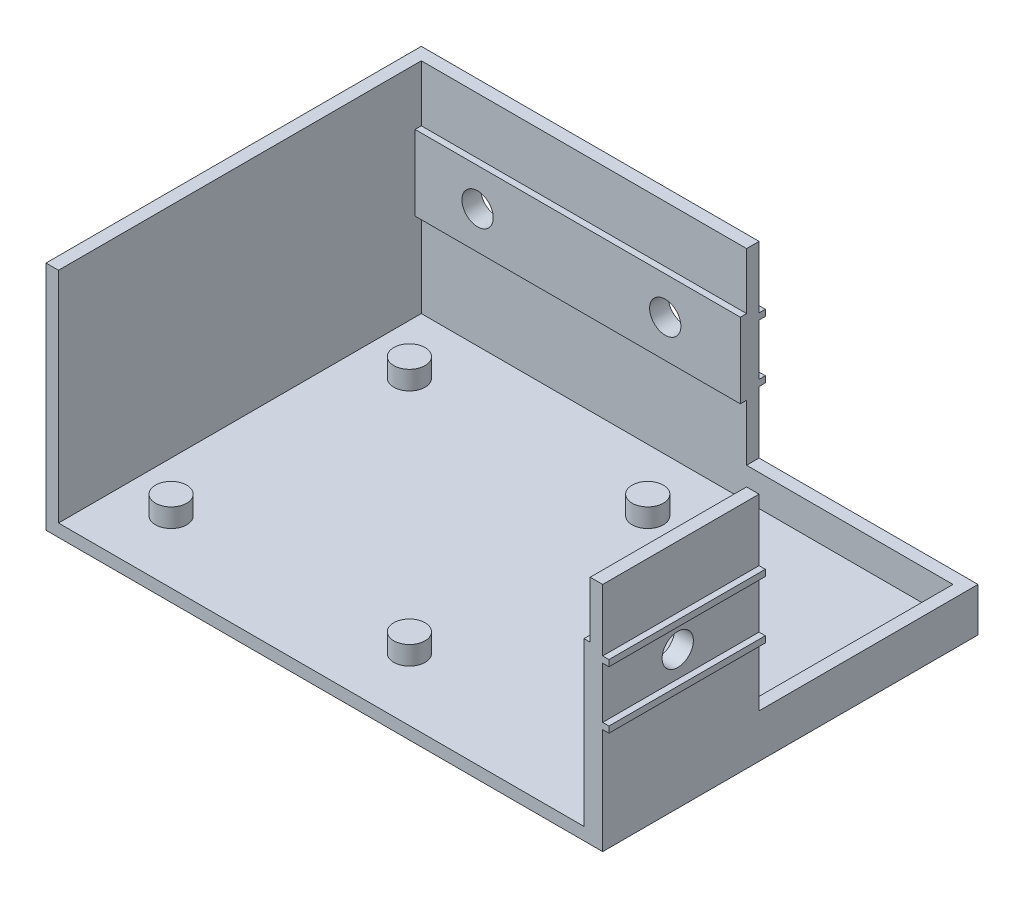
SolidWorks part; units mm, degrees
ref_plane "前视基准面" through (0, 0, 0) normal (0, 0, 1) x (1, 0, 0)
ref_plane "上视基准面" through (0, 0, 0) normal (0, 1, 0) x (1, 0, 0)
ref_plane "右视基准面" through (0, 0, 0) normal (1, 0, 0) x (0, 0, -1)
sketch "底座图" plane through (0, 0, 0) normal (0, 1, 0) x (1, 0, 0)
  line L1 (0, 60) -> (89, 60)
  line L2 (0, 60) -> (0, 0)
  line L3 (0, 0) -> (89, 0)
  line L4 (89, 60) -> (89, 0)
  dimension "D1" = 60
  dimension "D2" = 89
extrude "底座" add sketch "底座图" along normal blind 2
sketch "螺丝柱接口" plane through (0, 2, 0) normal (0, 1, 0) x (1, 0, 0)
  line L1 (0, 0) -> (89, 0) construction
  line L3 (0, 60) -> (0, 0) construction
  circle A0 centre (10, 10) radius 2.5
  circle A1 centre (48.1, 10) radius 2.5
  circle A2 centre (48.1, 48.1) radius 2.5
  circle A3 centre (10, 48.1) radius 2.5
  dimension "D5" = 38.1
  dimension "D7" = 5
  dimension "D1" = 10
  dimension "D2" = 10
  dimension "D4" = 2
  dimension "D6" = 38.1
  dimension "D3" = 2
extrude "螺丝柱" add sketch "螺丝柱接口" along normal blind 3
sketch "侧壁图" plane through (0, 2, 0) normal (0, 1, 0) x (1, 0, 0)
  line L8 (2, 58) -> (2, 2)
  line L9 (2, 2) -> (87, 2)
  line L10 (87, 2) -> (87, 58)
  line L11 (87, 58) -> (2, 58)
  line L12 (2, 58) -> (2, 0)
  line L14 (87, 0) -> (87, 58)
  line L15 (87, 58) -> (2, 58)
  dimension "D1" = 2
extrude "侧壁" add sketch "侧壁图" along normal blind 35 thin thin type one direction wall 2
sketch "草图4" plane through (0, 37, 0) normal (0, 1, 0) x (1, 0, 0)
  line L1 (89, 60) -> (54, 60)
  line L2 (89, 60) -> (89, 25)
  line L3 (89, 25) -> (54, 25)
  line L4 (54, 60) -> (54, 25)
  dimension "D1" = 35
  dimension "D2" = 35
extrude "连接件缺口处" cut sketch "草图4" against normal blind 30
sketch "草图8" plane through (87, 0, 0) normal (-1, 0, 0) x (0, 0, 1)
  line L0 (-25, 7) -> (-25, 37) construction
  line L1 (-25, 28) -> (0, 28)
  line L2 (-25, 28) -> (-25, 2)
  line L3 (-25, 2) -> (0, 2)
  line L4 (0, 28) -> (0, 2)
  line L6 (0, 37) -> (-25, 37) construction
  line L7 (0, 2) -> (-58, 2) construction
  dimension "D1" = 9
  dimension "D2" = 0
extrude "内凸层（侧）" add sketch "草图8" along normal blind 1
sketch "草图10" plane through (86, 0, 0) normal (-1, 0, 0) x (0, 0, 1)
  line L0 (0, 37) -> (-25, 37) construction
  line L4 (0, 2) -> (0, 28) construction
  circle A0 centre (-12, 22) radius 2.5
  dimension "D1" = 5
  dimension "D2" = 15
  dimension "D3" = 12
extrude "安装孔（侧）" cut sketch "草图10" against normal through all
sketch "草图11" plane through (89, 0, 0) normal (1, 0, 0) x (0, 0, -1)
  line L0 (0, 37) -> (0, 0) construction
  line L1 (0, 27.1) -> (25, 27.1)
  line L2 (0, 27.1) -> (0, 26.1)
  line L3 (0, 26.1) -> (25, 26.1)
  line L4 (25, 27.1) -> (25, 26.1)
  line L5 (25, 7) -> (25, 37) construction
  line L7 (25, 16.9) -> (25, 17.9)
  line L8 (0, 17.9) -> (25, 17.9)
  line L9 (0, 16.9) -> (0, 17.9)
  line L10 (0, 16.9) -> (25, 16.9)
  dimension "D3" = 4.1
  dimension "D1" = 1
extrude "安装纹路（侧）" add sketch "草图11" along normal blind 1
sketch "草图7" plane through (0, 0, -58) normal (0, 0, 1) x (1, 0, 0)
  line L0 (54, 37) -> (54, 7) construction
  line L1 (54, 28) -> (2, 28)
  line L2 (54, 28) -> (54, 16)
  line L3 (54, 16) -> (2, 16)
  line L4 (2, 28) -> (2, 16)
  line L5 (2, 37) -> (2, 2) construction
  line L6 (54, 37) -> (2, 37) construction
  point P8 (54, 22)
  dimension "D1" = 12
  dimension "D2" = 15
extrude "内凸层（后）" add sketch "草图7" along normal blind 1
sketch "安装孔图（后）" plane through (0, 0, -57) normal (0, 0, 1) x (1, 0, 0)
  line L0 (2, 28) -> (2, 16) construction
  line L2 (54, 37) -> (2, 37) construction
  circle A0 centre (12, 22) radius 2.5
  circle A1 centre (42, 22) radius 2.5
  dimension "D1" = 10
  dimension "D2" = 5
  dimension "D5" = 30
  dimension "D3" = 15
  dimension "D4" = 2
extrude "安装孔（后）" cut sketch "安装孔图（后）" against normal through all
sketch "草图12" plane through (0, 0, -60) normal (0, 0, -1) x (-1, 0, 0)
  line L0 (-54, 7) -> (-54, 37) construction
  line L1 (-54, 27.1) -> (0, 27.1)
  line L2 (-54, 27.1) -> (-54, 26.1)
  line L3 (-54, 26.1) -> (0, 26.1)
  line L4 (0, 27.1) -> (0, 26.1)
  line L5 (0, 37) -> (0, 0) construction
  line L7 (0, 16.9) -> (0, 17.9)
  line L8 (-54, 17.9) -> (0, 17.9)
  line L9 (-54, 16.9) -> (-54, 17.9)
  line L10 (-54, 16.9) -> (0, 16.9)
  dimension "D1" = 1
  dimension "D2" = 4.1
extrude "安装纹路（后）" add sketch "草图12" along normal blind 1
